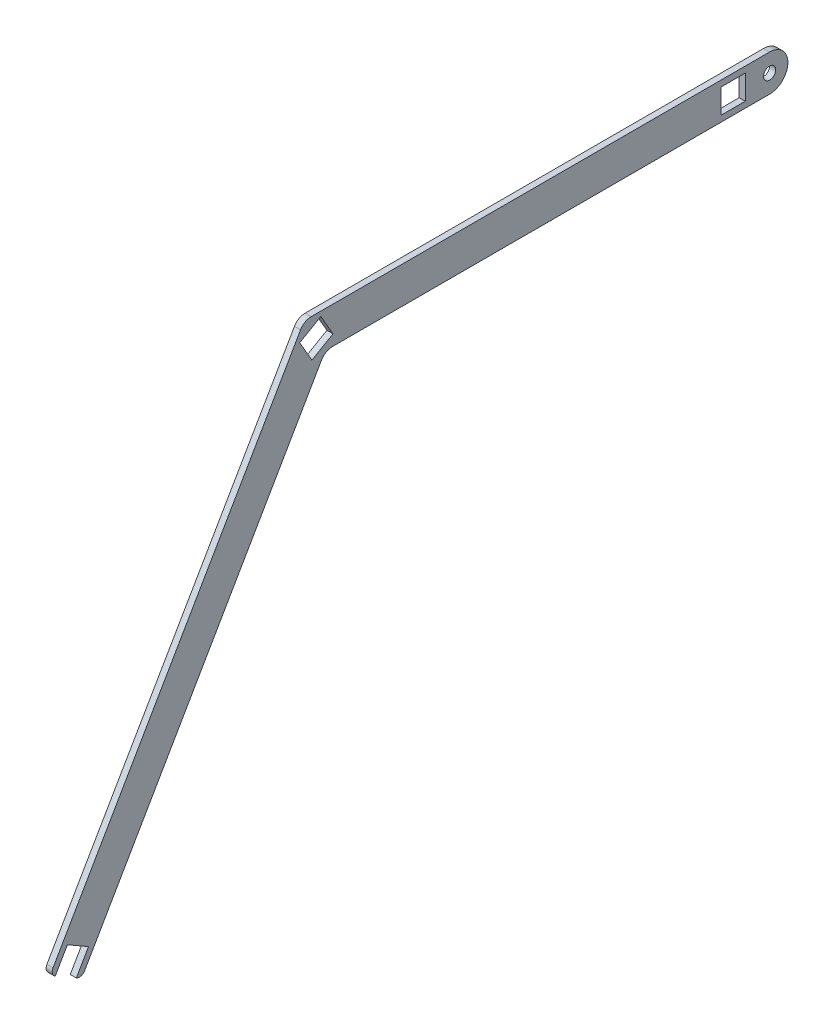
SolidWorks part; units mm, degrees
ref_plane "Plan de face" through (0, 0, 0) normal (0, 0, 1) x (1, 0, 0)
ref_plane "Plan de dessus" through (0, 0, 0) normal (0, 1, 0) x (1, 0, 0)
ref_plane "Plan de droite" through (0, 0, 0) normal (1, 0, 0) x (0, 0, -1)
sketch "Esquisse1" plane through (0, 0, 0) normal (1, 0, 0) x (0, 0, -1)
  line L0 (0, 30) -> (-764.641, 30)
  line L1 (-764.641, 30) -> (-1181.9615, -692.8203)
  line L2 (-1181.9615, -692.8203) -> (-1130, -722.8203) construction
  line L3 (-1130, -722.8203) -> (-730, -30)
  line L4 (-730, -30) -> (0, -30)
  line L5 (-730, -30) -> (-730, 30) construction
  line L6 (-730, -30) -> (-799.282, -30) construction
  line L7 (-730, -30) -> (-781.9615, 0) construction
  line L8 (0, 0) -> (-730, 0) construction
  line L9 (-1155.9808, -707.8203) -> (-755.9808, -15) construction
  line L10 (-755.9808, -15) -> (-747.3205, 0) construction
  line L11 (-730, 0) -> (-747.3205, 0) construction
  line L12 (-40, 20) -> (-80, -20) construction
  line L13 (-40, 20) -> (-80, 20)
  line L14 (-40, 20) -> (-40, -20)
  line L15 (-40, -20) -> (-80, -20)
  line L16 (-80, 20) -> (-80, -20)
  line L17 (-764.641, 30) -> (-730, -30) construction
  line L18 (-737.1132, 22.3205) -> (-771.7543, 2.3205)
  line L19 (-771.7543, 2.3205) -> (-751.7543, -32.3205)
  line L20 (-751.7543, -32.3205) -> (-717.1132, -12.3205)
  line L21 (-717.1132, -12.3205) -> (-737.1132, 22.3205)
  line L22 (-717.1132, -12.3205) -> (-771.7543, 2.3205) construction
  line L23 (-1181.9615, -692.8203) -> (-1173.3013, -697.8203)
  line L24 (-1173.3013, -697.8203) -> (-1153.3013, -663.1793)
  line L25 (-1153.3013, -663.1793) -> (-1118.6603, -683.1793)
  line L26 (-1118.6603, -683.1793) -> (-1138.6603, -717.8203)
  line L27 (-1138.6603, -717.8203) -> (-1130, -722.8203)
  circle A0 centre (0, 0) radius 10
  circle A1 centre (0, 0) radius 30 construction
  arc A2 (0, 30) -> (0, -30) centre (0, 0) cw
  point P21 (-60, 0)
  point P22 (-744.4338, -5)
  point P26 (-1135.9808, -673.1793)
  dimension "D1" = 60
  dimension "D2" = 20
  dimension "D4" = 730
  dimension "D3" = 60
  dimension "D5" = 800
  dimension "D6" = 120
  dimension "D7" = 40
  dimension "D8" = 40
  dimension "D9" = 40
  dimension "D10" = 40
  dimension "D11" = 40
  dimension "D12" = 25
  dimension "D13" = 40
  dimension "D14" = 40
extrude "Boss.-Extru.1" add sketch "Esquisse1" along normal blind 10
fillet "Congé1" radius 10 2 edges at (5, -692.8203, 1181.9615) (5, -722.8203, 1130)
fillet "Congé2" radius 20 2 edges at (5, -30, 730) (5, 30, 764.641)
